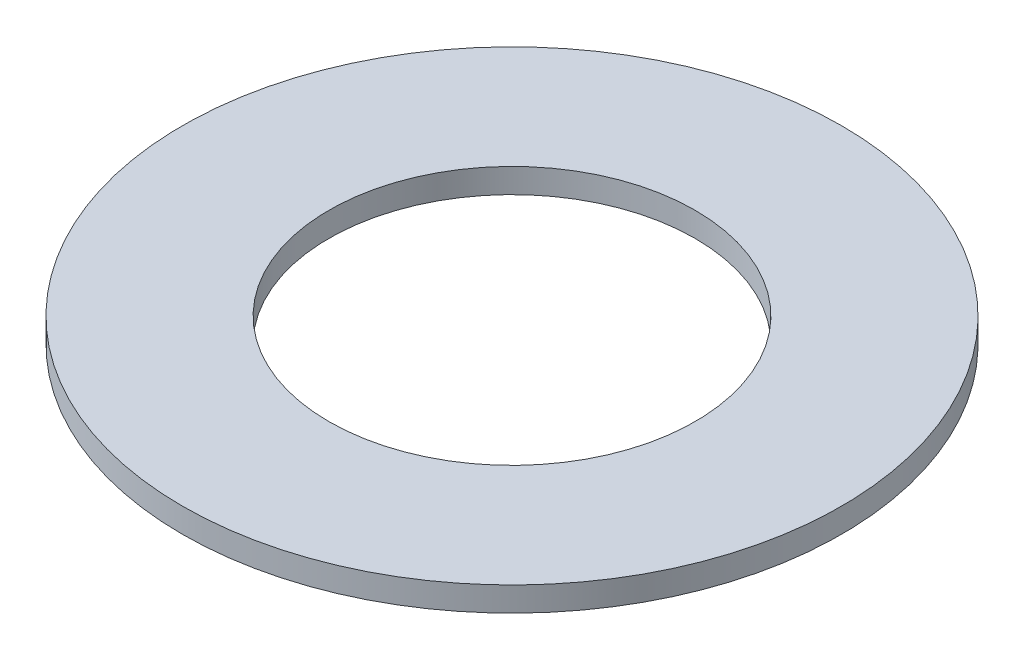
SolidWorks part; units mm, degrees
material "1060 Alloy"
ref_plane "Front Plane" through (0, 0, 0) normal (0, 0, 1) x (1, 0, 0)
ref_plane "Top Plane" through (0, 0, 0) normal (0, 1, 0) x (1, 0, 0)
ref_plane "Right Plane" through (0, 0, 0) normal (1, 0, 0) x (0, 0, -1)
sketch "Sketch1" plane through (0, 0, 0) normal (0, 1, 0) x (1, 0, 0)
  circle A0 centre (0, 0) radius 13.5
  dimension "D1" = 27
extrude "Boss-Extrude1" add sketch "Sketch1" along normal blind 1
sketch "Sketch4" plane through (0, 1, 0) normal (0, 1, 0) x (1, 0, 0)
  circle A1 centre (0, 0) radius 7.5
  dimension "D3" = 15
extrude "Cut-Extrude3" cut sketch "Sketch4" against normal through all both and the other way through all
